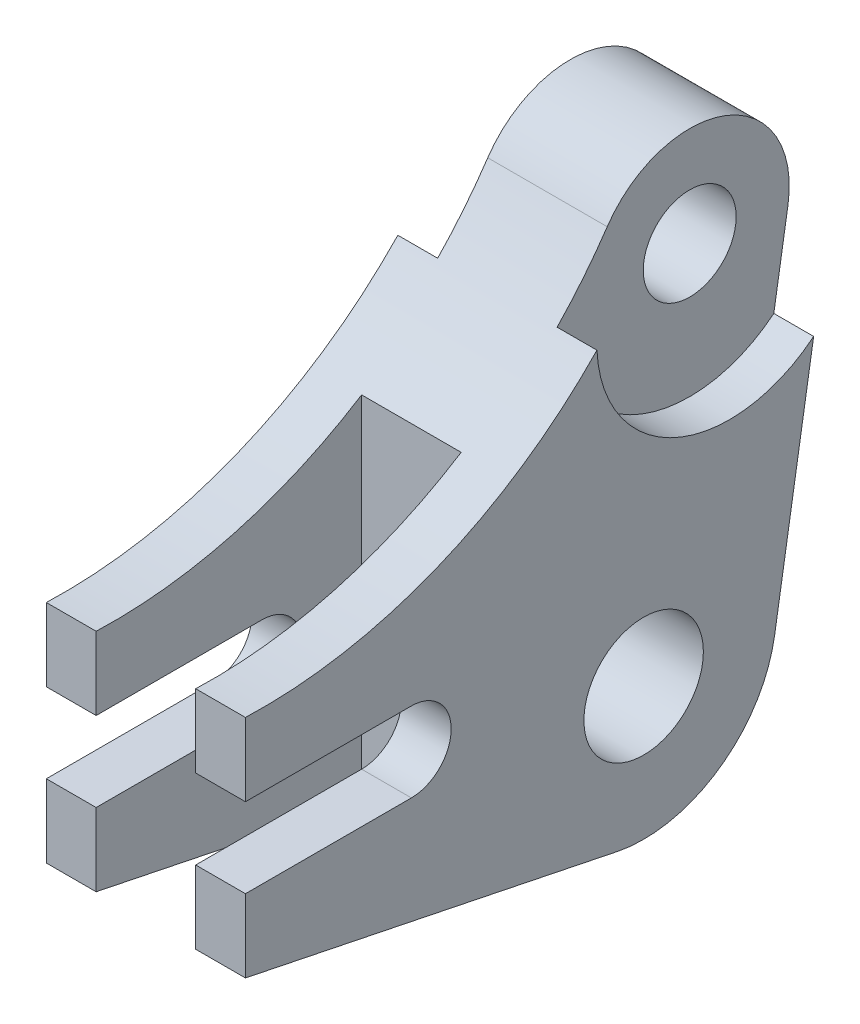
SolidWorks part; units mm, degrees
ref_plane "Ön Düzlem" through (0, 0, 0) normal (0, 0, 1) x (1, 0, 0)
ref_plane "Üst Düzlem" through (0, 0, 0) normal (0, 1, 0) x (1, 0, 0)
ref_plane "Sağ Düzlem" through (0, 0, 0) normal (1, 0, 0) x (0, 0, -1)
sketch "Çizim2" plane through (0, 0, 0) normal (1, 0, 0) x (0, 0, -1)
  line L0 (0, 0) -> (0, 92.4035) construction
  line L1 (12.941, 48.2963) -> (11.1292, 41.5348) construction
  line L2 (19.7393, -3.2186) -> (27.7454, 45.8824)
  line L3 (-35, 2.9127) -> (-60, 2.9127)
  line L4 (-35, 14.9127) -> (-60, 14.9127)
  line L7 (-60, 2.9127) -> (-60, -8.0873)
  line L8 (-60, -8.0873) -> (-4.0111, -19.5937)
  line L9 (9.0587, 33.8074) -> (0, 0) construction
  line L10 (-60, 25.9127) -> (-60, 99.7762) construction
  line L11 (-60, 25.9127) -> (-60, 14.9127)
  circle A0 centre (12.941, 48.2963) radius 7
  circle A1 centre (0, 0) radius 9
  arc A3 (27.7454, 45.8824) -> (0.5102, 56.6913) centre (12.941, 48.2963) ccw
  arc A4 (-35, 2.9127) -> (-35, 14.9127) centre (-35, 8.9127) ccw
  arc A7 (-4.0111, -19.5937) -> (19.7393, -3.2186) centre (0, 0) ccw
  arc A8 (-60, 25.9127) -> (0.5102, 56.6913) centre (-57.5, 95.8681) ccw
  point P10 (0, 20)
  dimension "D2" = 18
  dimension "D3" = 2.5
  dimension "D4" = 14
  dimension "D5" = 30
  dimension "D7" = 12
  dimension "D8" = 25
  dimension "D12" = 70
  dimension "D1" = 15
  dimension "D6" = 50
  dimension "D9" = 25
  dimension "D10" = 60
  dimension "D11" = 17
extrude "Yükseklik-Ekstrüzyon1" add sketch "Çizim2" along normal mid plane 30
sketch "Çizim3" plane through (15, 0, 0) normal (1, 0, 0) x (0, 0, -1)
  circle A0 centre (12.941, 48.2963) radius 20
  dimension "D1" = 40
extrude "Kes-Ekstrüzyon1" cut sketch "Çizim3" against normal blind 6
mirror "Aynalama1" about plane through (0, 0, 0) normal (1, 0, 0) of "Kes-Ekstrüzyon1"
ref_plane "Düzlem1" through (0, 25.8681, 0) normal (0, 1, 0) x (1, 0, 0)
sketch "Çizim5" plane through (0, 25.8681, 0) normal (0, 1, 0) x (1, 0, 0)
  line L0 (15, -60) -> (-15, -60) construction
  line L1 (-7.4964, -20) -> (7.5036, -20)
  line L2 (-7.4964, -20) -> (-7.4964, -60)
  line L3 (-7.4964, -60) -> (7.5036, -60)
  line L4 (7.5036, -20) -> (7.5036, -60)
  point P0 (0, -39.7563)
  dimension "D1" = 15
  dimension "D2" = 40
extrude "Kes-Ekstrüzyon4" cut sketch "Çizim5" against normal through all and the other way blind 18
